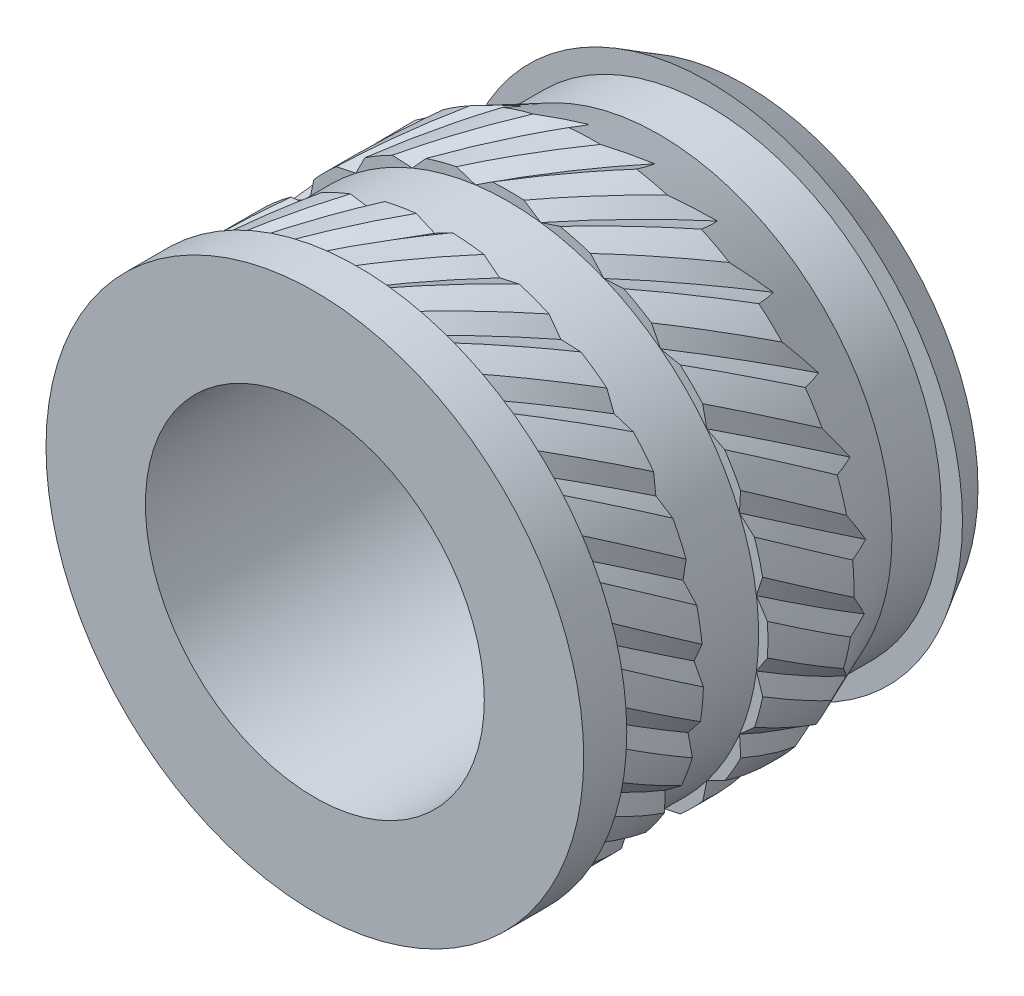
SolidWorks part; units mm, degrees
ref_plane "Front Plane" through (0, 0, 0) normal (0, 0, 1) x (1, 0, 0)
ref_plane "Top Plane" through (0, 0, 0) normal (0, 1, 0) x (1, 0, 0)
ref_plane "Right Plane" through (0, 0, 0) normal (1, 0, 0) x (0, 0, -1)
sketch "Sketch1" plane through (0, 0, 0) normal (1, 0, 0) x (0, 0, -1)
  line L0 (-3.81, 0) -> (3.81, 0) construction
  line L1 (-3.81, 3) -> (-3.81, 4.76)
  line L2 (-3.81, 4.76) -> (-3.048, 4.76)
  line L3 (-3.048, 4.76) -> (-3.048, 4.595)
  line L4 (-3.048, 4.595) -> (-1.524, 4.595)
  line L5 (-1.524, 4.595) -> (-1.524, 4.43)
  line L6 (-1.524, 4.43) -> (-0.385, 4.43)
  line L7 (-0.385, 4.43) -> (-0.385, 4.595)
  line L9 (1.139, 4.595) -> (2.286, 4.1199)
  line L13 (2.286, 4.1199) -> (3.1603, 4.1199)
  line L14 (3.1603, 4.1199) -> (3.1603, 4.495)
  line L15 (3.1603, 4.495) -> (3.81, 4.1199)
  line L16 (3.81, 4.1199) -> (3.81, 3)
  line L17 (-3.81, 4.495) -> (3.81, 4.495) construction
  line L18 (3.81, 0) -> (3.81, 4.495) construction
  line L19 (-3.81, 0) -> (-3.81, 4.76) construction
  line L20 (-0.385, 4.595) -> (1.139, 4.595)
  line L21 (-3.81, 3) -> (3.81, 3)
  line L23 (-4.7475, 3.1083) -> (-4.2475, 2.2422) construction
  line L24 (-3.81, -4.495) -> (3.81, -4.495) construction
  line L25 (-4.2475, 2.2422) -> (-3.7475, 3.1083) construction
  line L26 (-3.7475, 3.1083) -> (-4.7475, 3.1083) construction
  line L27 (-4.685, 3) -> (-3.81, 3) construction
  line L28 (-4.2475, 3.1083) -> (-4.2475, 3) construction
  line L29 (-4.2475, 3) -> (-4.2475, 2.3505) construction
  line L30 (-4.2475, 2.3505) -> (-4.2475, 2.2422) construction
  line L31 (-4.31, 2.3505) -> (-4.185, 2.3505)
  line L32 (-4.7163, 3.0541) -> (-3.7788, 3.0541)
  line L33 (-4.185, 2.3505) -> (-3.7788, 3.0541)
  line L34 (-4.31, 2.3505) -> (-4.7163, 3.0541)
  line L35 (-3.81, 4.43) -> (3.81, 4.43) construction
  line L36 (-3.81, -4.43) -> (3.81, -4.43) construction
  point P36 (-4.2475, 3.0541)
  dimension "Installed Length" = 7.62
  dimension "Dia A" = 9.52
  dimension "Dia B" = 8.99
  dimension "Thread Dia" = 6
  dimension "D6" = 30
  dimension "D8" = 1.524
  dimension "D4" = 22.5
  dimension "Thread Pitch" = 1
  dimension "D2" = 0.125
  dimension "Max Hole Dia" = 8.86
  dimension "Knurling Length" = 5.334
  dimension "D1" = 8.2398
  dimension "D3" = 0.762
ref_plane "Plane1" through (0, 0, 3.048) normal (0, 0, 1) x (1, 0, 0)
sketch "Sketch2" plane through (0, 0, 3.048) normal (0, 0, 1) x (1, 0, 0)
  line L0 (0, 0) -> (0, 4.595) construction
  line L1 (-0.3387, 4.5925) -> (0, 4.43)
  line L2 (0.3387, 4.5925) -> (0, 4.43)
  line L3 (-0.3205, 4.5838) -> (0, 0) construction
  line L4 (0.3205, 4.5838) -> (0, 0) construction
  line L5 (0, 0) -> (-0.5998, 4.5557) construction
  line L6 (0, 0) -> (0.5998, 4.5557) construction
  line L7 (0, 0) -> (3.2492, 3.2492) construction
  line L8 (0, 0) -> (0, -3.1083) construction
  line L9 (0, 0) -> (1.5541, -2.6918) construction
  circle A0 centre (0, 0) radius 4.43 construction
  circle A1 centre (0, 0) radius 4.595 construction
  circle A3 centre (0, 0) radius 3.1083
  arc A4 (-0.3387, 4.5925) -> (0.3387, 4.5925) centre (0, 0) cw
  dimension "Knurl Angle" = 8
  dimension "Pattern Angle" = 15
  dimension "Helix Angle" = 45
  dimension "D1" = 30
sketch "Sketch3" plane through (0, 0, 0) normal (1, 0, 0) x (0, 0, -1)
  line L0 (-3.81, 3) -> (-3.81, 4.76) construction
  line L1 (-3.81, 4.76) -> (-3.048, 4.76) construction
  line L2 (-3.048, 4.76) -> (-3.048, 4.595) construction
  line L3 (-3.048, 4.595) -> (-1.524, 4.595) construction
  line L4 (-1.524, 4.595) -> (-1.524, 4.43) construction
  line L5 (-1.524, 4.43) -> (-0.385, 4.43) construction
  line L6 (-0.385, 4.43) -> (-0.385, 4.595) construction
  line L8 (1.139, 4.595) -> (2.286, 4.1199) construction
  line L12 (2.286, 4.1199) -> (3.1603, 4.1199) construction
  line L13 (3.1603, 4.1199) -> (3.1603, 4.495) construction
  line L14 (3.1603, 4.495) -> (3.81, 4.1199) construction
  line L15 (3.81, 4.1199) -> (3.81, 3) construction
  line L16 (-3.81, 3) -> (3.81, 3) construction
  line L17 (-3.81, 3) -> (-3.81, 4.76)
  line L18 (-3.81, 4.76) -> (-3.048, 4.76)
  line L19 (-3.048, 4.76) -> (-3.048, 4.595)
  line L20 (-3.048, 4.595) -> (-1.524, 4.595)
  line L21 (-1.524, 4.595) -> (-1.524, 4.43)
  line L22 (-1.524, 4.43) -> (-0.385, 4.43)
  line L23 (-0.385, 4.43) -> (-0.385, 4.595)
  line L25 (1.139, 4.595) -> (2.286, 4.1199)
  line L29 (2.286, 4.1199) -> (3.1603, 4.1199)
  line L30 (3.1603, 4.1199) -> (3.1603, 4.495)
  line L31 (3.1603, 4.495) -> (3.81, 4.1199)
  line L32 (3.81, 4.1199) -> (3.81, 3)
  line L33 (-3.81, 3) -> (3.81, 3)
  line L34 (-0.385, 4.595) -> (1.139, 4.595) construction
  line L35 (-0.385, 4.595) -> (1.139, 4.595)
revolve "Revolve1" add sketch "Sketch3" angle 360 about L0
sketch "Sketch4" plane through (0, 0, 3.048) normal (0, 0, 1) x (1, 0, 0)
  circle A2 centre (0, 0) radius 4.595 construction
  circle A3 centre (0, 0) radius 4.595
sketch "Sketch6" [suppressed] plane through (0, 0, 3.81) normal (0, 0, 1) x (1, 0, 0)
  circle A0 centre (0, 0) radius 3
curve "Helix/Spiral2" [suppressed] pitch 1 height 8.62 turns 8.62
sketch "Sketch7" [suppressed] plane through (0, 0, 0) normal (1, 0, 0) x (0, 0, -1)
  line L0 (-4.31, 2.3505) -> (-4.185, 2.3505) construction
  line L1 (-4.31, 2.3505) -> (-4.7163, 3.0541) construction
  line L2 (-4.7163, 3.0541) -> (-3.7788, 3.0541) construction
  line L3 (-4.185, 2.3505) -> (-3.7788, 3.0541) construction
  line L4 (-4.31, 2.3505) -> (-4.185, 2.3505)
  line L5 (-4.31, 2.3505) -> (-4.7163, 3.0541)
  line L6 (-4.7163, 3.0541) -> (-3.7788, 3.0541)
  line L7 (-4.185, 2.3505) -> (-3.7788, 3.0541)
sweep "Sweep1" [suppressed] add profiles "Sketch7" path "Helix/Spiral2"
sketch "Sketch8" [suppressed] plane through (0, 0, 3.81) normal (0, 0, 1) x (1, 0, 0)
  circle A0 centre (0, 0) radius 3.1083
extrude "Cut-Extrude1" [suppressed] cut sketch "Sketch8" against normal through all draft 45 and the other way through all
mirror "Mirror1" [suppressed] about plane through (0, 0, 0) normal (0, 0, 1)
curve "Helix/Spiral1" pitch 42.672 height 5.334 radius 4.595 centre (0, 0, 3.048) axis (0, 0, -1) start towards (0, 1, 0)
sketch "Sketch5" plane through (0, 0, 3.048) normal (0, 0, 1) x (1, 0, 0)
  line L0 (-0.3387, 4.5925) -> (0, 4.43) construction
  line L1 (0.3387, 4.5925) -> (0, 4.43) construction
  line L2 (-0.3387, 4.5925) -> (0, 4.43)
  line L3 (0.3387, 4.5925) -> (0, 4.43)
  arc A2 (0.3387, 4.5925) -> (-0.3387, 4.5925) centre (0, 0) ccw construction
  arc A3 (0.3387, 4.5925) -> (-0.3387, 4.5925) centre (0, 0) ccw
sweep "Cut-Sweep1" cut profiles "Sketch5" path "Helix/Spiral1" align with end faces yes
pattern_circular "CirPattern1" count 24 over 360 about axis through (0, 0, 3.81) along (0, 0, -1) of "Cut-Sweep1"
equation "\"D8@Sketch1\"=\"Installed Length@Sketch1\" * .2"
equation "\"D4@Helix/Spiral1\"=\"Knurling Length@Sketch1\"*(360/\"Helix Angle@Sketch2\")"
equation "\"D3@Helix/Spiral1\"=\"Knurling Length@Sketch1\""
equation "\"D1@CirPattern1\"=\"D3@CirPattern1\"/\"Pattern Angle@Sketch2\""
equation "\"D2@Sketch1\" = \"Thread Pitch@Sketch1\" / 8"
equation "\"D4@Helix/Spiral2\"=\"Thread Pitch@Sketch1\""
equation "\"D3@Helix/Spiral2\" = \"Installed Length@Sketch1\" + \"Thread Pitch@Sketch1\""
equation "\"Knurling Length@Sketch1\"=\"Installed Length@Sketch1\" * .7"
equation "\"D1@Sketch1\"=\"Max Hole Dia@Sketch1\"*.93"
equation "\"D3@Sketch1\"=\"Installed Length@Sketch1\"*.1"
